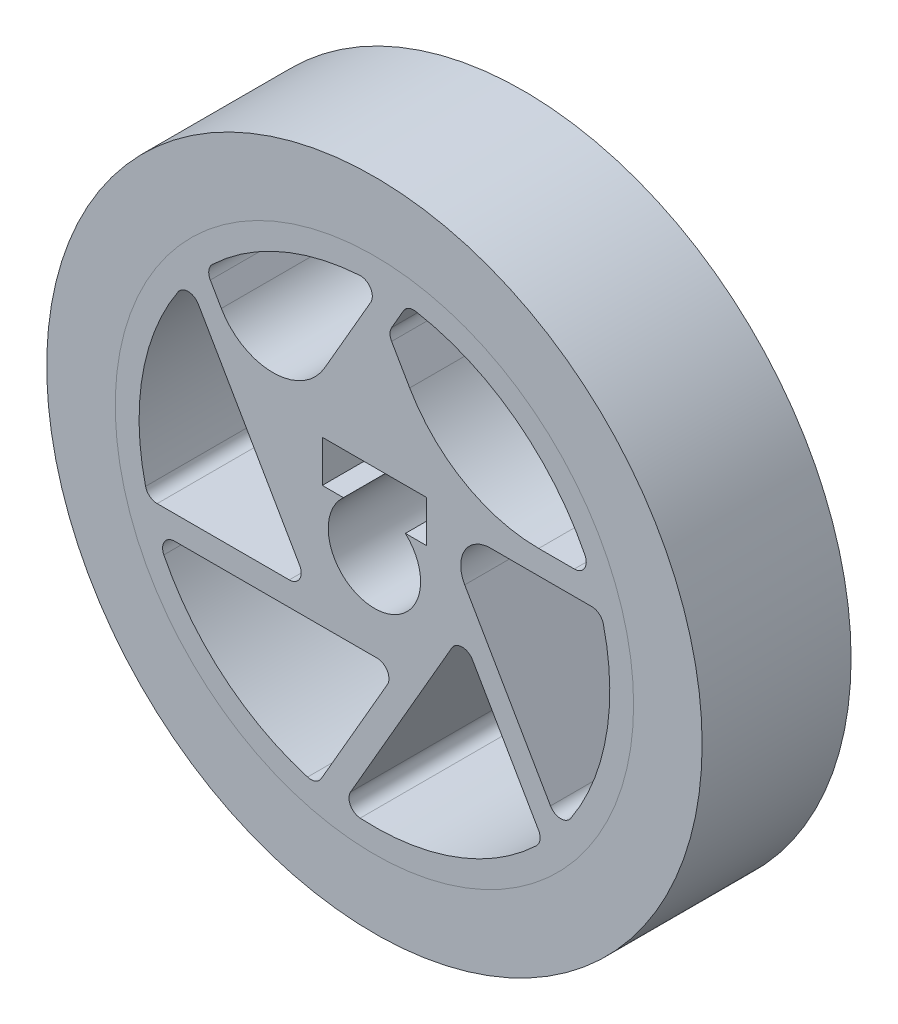
SolidWorks part; units mm, degrees
other "tire-mock"
other "hub"
ref_plane "Front Plane" through (0, 0, 0) normal (0, 0, 1) x (1, 0, 0)
ref_plane "Top Plane" through (0, 0, 0) normal (0, 1, 0) x (1, 0, 0)
ref_plane "Right Plane" through (0, 0, 0) normal (1, 0, 0) x (0, 0, -1)
other "Center of Mass"
sketch "Sketch1" plane through (0, 0, 0) normal (0, 0, 1) x (1, 0, 0)
  line L0 (2.0785, 2.3) -> (3.5, 2.3)
  line L1 (3.5, 2.3) -> (3.5, 5.1)
  line L2 (3.5, 5.1) -> (-3.5, 5.1)
  line L3 (-3.5, 5.1) -> (-3.5, 2.3)
  line L4 (-3.5, 2.3) -> (-2.0785, 2.3)
  line L5 (-1.9261, 2.3) -> (1.9261, 2.3) construction
  line L6 (-6.8127, 0) -> (-12.4381, 9.7434)
  line L7 (3.4064, -5.9) -> (6.8127, 0) construction
  line L8 (6.8127, 0) -> (3.4064, 5.9) construction
  line L9 (3.4064, 5.9) -> (-3.4064, 5.9) construction
  line L10 (-3.4064, 5.9) -> (-6.8127, 0) construction
  line L11 (-6.8127, 0) -> (-3.4064, -5.9) construction
  line L12 (-3.4064, -5.9) -> (3.4064, -5.9) construction
  line L13 (-3.4064, -5.9) -> (-14.6571, -5.9)
  line L14 (3.4064, -5.9) -> (-2.219, -15.6434)
  line L15 (6.8127, 0) -> (12.4381, -9.7434)
  line L16 (-5.889, 1.6) -> (-11.3257, 11.0167) construction
  line L17 (5.889, -1.6) -> (11.3257, -11.0167)
  line L18 (1.5588, -5.9) -> (-3.8779, -15.3167)
  line L19 (-4.3301, -4.3) -> (-15.2036, -4.3)
  line L20 (3.4064, 5.9) -> (14.6571, 5.9) construction
  line L21 (4.3301, 4.3) -> (15.2036, 4.3)
  line L22 (-11.3257, 11.0167) -> (-6.8127, 3.2)
  line L23 (-6.8127, 3.2) -> (-3.3459, 9.2048)
  line L24 (-3.3459, 9.2048) -> (3.3459, 9.2048) construction
  line L25 (3.3459, 9.2048) -> (5.2539, 5.9)
  line L26 (5.2539, 5.9) -> (14.6571, 5.9)
  line L29 (-6.8127, 0) -> (-4.3301, -4.3)
  line L30 (-3.4064, -5.9) -> (1.5588, -5.9)
  line L31 (3.4064, -5.9) -> (5.889, -1.6)
  line L32 (6.8127, 0) -> (4.3301, 4.3)
  line L33 (-3.3459, 9.2048) -> (0.458, 15.7934)
  line L34 (2.219, 15.6434) -> (-1.4983, 9.2048)
  line L35 (3.3459, 9.2048) -> (-1.4983, 9.2048)
  line L36 (9.9555, 5.9) -> (9.9555, 4.3) construction
  line L37 (-1.4439, 12.4991) -> (-0.0583, 11.6991) construction
  circle A0 centre (0, 0) radius 3 construction
  circle A1 centre (0, 0) radius 3.1 construction
  arc A2 (-2.0785, 2.3) -> (2.0785, 2.3) centre (0, 0) ccw
  circle A3 centre (0, 0) radius 5.9 construction
  circle A4 centre (0, 0) radius 22 construction
  circle A6 centre (0, 0) radius 17.4
  circle A7 centre (0, 0) radius 15.8 construction
  arc A8 (0.458, 15.7934) -> (-11.3257, 11.0167) centre (0, 0) ccw
  arc A9 (-12.4381, 9.7434) -> (-15.2036, -4.3) centre (0, 0) ccw
  arc A10 (-3.8779, -15.3167) -> (-14.6571, -5.9) centre (0, 0) cw
  arc A11 (11.3257, -11.0167) -> (-2.219, -15.6434) centre (0, 0) cw
  arc A12 (15.2036, 4.3) -> (12.4381, -9.7434) centre (0, 0) cw
  arc A13 (14.6571, 5.9) -> (2.219, 15.6434) centre (0, 0) ccw
  point P13 (0, -3)
  point P43 (0, 9.2048)
  point P55 (-17.4, 0)
  point P56 (17.4, 0)
  point P58 (0, -17.4)
  point P59 (0, 17.4)
  point P61 (-15.8, 0)
  dimension "D1" = 6
  dimension "D7" = 44
  dimension "D3" = 7
  dimension "D4" = 2.8
  dimension "D5" = 5.3
  dimension "D6" = 0.8
  dimension "D10" = 1.6
  dimension "D11" = 4.1048
  dimension "D12" = 1.6
  dimension "D2" = 0.1
  dimension "D8" = 4.6
  dimension "D9" = 1.6
extrude "Boss-Extrude1" add sketch "Sketch1" along normal blind 10
ref_axis "Axis1" through (0, 0, 10) along (0, 0, -1)
sketch "Sketch9" plane through (0, 0, 0) normal (0, 0, -1) x (-1, 0, 0)
  line L0 (-3.3459, 9.2048) -> (-0.9238, 13.4)
  line L1 (-3.3459, 9.2048) -> (-5.2539, 5.9) construction
  line L2 (-2.219, 15.6434) -> (1.4983, 9.2048) construction
  line L3 (-0.9238, 13.4) -> (1.4983, 9.2048)
  line L4 (1.4983, 9.2048) -> (-3.3459, 9.2048)
extrude "Boss-Extrude3" add sketch "Sketch9" against normal up to surface (10 mm away) up to face at (17.4, 0, 10)
sketch "Sketch10" plane through (0, 0, 0) normal (0, 0, -1) x (-1, 0, 0)
  line L0 (2.3094, 11) -> (5.4911, 16.5108)
  line L1 (3.3459, 9.2048) -> (-0.458, 15.7934) construction
  line L2 (5.4911, 16.5108) -> (9.1294, 14.8126)
  line L3 (9.1294, 14.8126) -> (4.6188, 7)
  line L4 (4.6188, 7) -> (2.3094, 11)
  line L5 (-3.3459, 9.2048) -> (-5.2539, 5.9) construction
  circle A0 centre (0, 0) radius 17.4 construction
  dimension "D1" = 4
  dimension "D2" = 4
extrude "Boss-Extrude6" [suppressed] add sketch "Sketch10" against normal up to surface (10 mm away) up to face at (6.0898, 10.6274, 10)
fillet "Fillet1" radius 0.8 4 edges at (5.889, -1.6, 5) (1.5588, -5.9, 5) (-4.3301, -4.3, 5) (0.9238, 13.4, 5)
fillet "Fillet2" radius 0.8 6 edges at (12.4381, -9.7434, 5) (14.6571, 5.9, 5) (-12.4381, 9.7434, 5) (-14.6571, -5.9, 5) (-2.219, -15.6434, 5) (0.458, 15.7934, 5)
fillet "Fillet3" radius 0.8 6 edges at (-15.2036, -4.3, 5) (-11.3257, 11.0167, 5) (15.2036, 4.3, 5) (11.3257, -11.0167, 5) (-3.8779, -15.3167, 5) (2.219, 15.6434, 5)
sketch "Sketch8" [suppressed] plane through (0, 0, 10) normal (0, 0, 1) x (1, 0, 0)
  line L1 (-3.4613, 18.0715) -> (3.4613, 18.0715)
  line L2 (-3.4613, 18.0715) -> (-3.4613, 9.4048)
  line L3 (-3.4613, 9.4048) -> (3.4613, 9.4048)
  line L4 (3.4613, 18.0715) -> (3.4613, 9.4048)
  line L5 (0, 9.4048) -> (0, 18.0715) construction
  line L6 (-3.4613, 13.7382) -> (3.4613, 13.7382) construction
  circle A0 centre (0, 0) radius 18.4 construction
  point P0 (0, 13.7382)
extrude "Boss-Extrude2" [suppressed] add sketch "Sketch8" against normal up to surface (10 mm away) up to face at (5.8574, 11.0938, 0)
sketch "Sketch2" plane through (0, 5.1, 0) normal (0, -1, 0) x (1, 0, 0)
  line L0 (0, 10) -> (0, 0) construction
  line L1 (3.5, 10) -> (-3.5, 10) construction
  line L2 (3.5, 0) -> (-3.5, 0) construction
  circle A0 centre (0, 5) radius 1.8
  dimension "D1" = 3.6
extrude "Cut-Extrude1" cut sketch "Sketch2" against normal up to surface (10.5971 mm away) up to face at (8.9602, 11.9789, 5)
sketch "Sketch6" plane through (0, 5.1, 0) normal (0, -1, 0) x (1, 0, 0)
  circle A0 centre (0, 5) radius 1.4
  dimension "D1" = 2.8
extrude "Cut-Extrude3" cut sketch "Sketch6" against normal through all
sketch "Sketch11" plane through (0, 0, 10) normal (0, 0, 1) x (1, 0, 0)
  circle A0 centre (0, 0) radius 22 construction
  circle A1 centre (0, 0) radius 22
  circle A2 centre (0, 0) radius 17.4 construction
  circle A3 centre (0, 0) radius 17.4
extrude "Boss-Extrude7" add sketch "Sketch11" against normal up to surface (10 mm away) separate body up to face at (5.8574, 11.0938, 0)
fillet "Fillet4" radius 10 1 edges at (5.2539, 5.9, 5)
fillet "Fillet5" radius 4 1 edges at (-6.8127, 3.2, 5)
fillet "Fillet6" radius 2 1 edges at (4.3301, 4.3, 5)
ref_plane "Plane1" [suppressed] through (0, 0, 5) normal (0, 0, 1) x (1, 0, 0)
sketch "Sketch12" [suppressed] plane through (0, 0, 5) normal (0, 0, 1) x (1, 0, 0)
  line L0 (14.225, 5.9) -> (14.7875, 4.3) construction
  line L1 (14.7875, 4.3) -> (3.6698, 14.9563) construction
  line L2 (3.6698, 14.9563) -> (-11.1177, 10.6563) construction
  line L3 (-11.1177, 10.6563) -> (-14.7875, -4.3) construction
  line L4 (-14.7875, -4.3) -> (-3.6698, -14.9563) construction
  line L5 (-3.6698, -14.9563) -> (11.1177, -10.6563) construction
  line L6 (11.1177, -10.6563) -> (14.7875, 4.3) construction
  line L7 (0, 0) -> (14.7875, 4.3)
  circle A0 centre (0, 0) radius 13.3368 construction
  point P13 (0, 0)
  point P14 (0, 0)
  point P15 (0, 0)
  point P16 (0, 0)
ref_plane "Plane2" [suppressed] through (14.7875, 4.3, 5) normal (0.9602, 0.2792, 0) x (0, 0, -1)
sketch "Sketch13" [suppressed] plane through (14.7875, 4.3, 5) normal (0.9602, 0.2792, 0) x (0, 0, -1)
  circle A0 centre (0, 0) radius 1.35
  point P2 (0, 0)
  dimension "D1" = 2.7
extrude "Cut-Extrude4" [suppressed] cut sketch "Sketch13" against normal blind 7 and the other way through all
pattern_circular "CirPattern1" [suppressed] count 6 over 360 about axis through (0, 0, 10) along (0, 0, -1) of bodies 113
